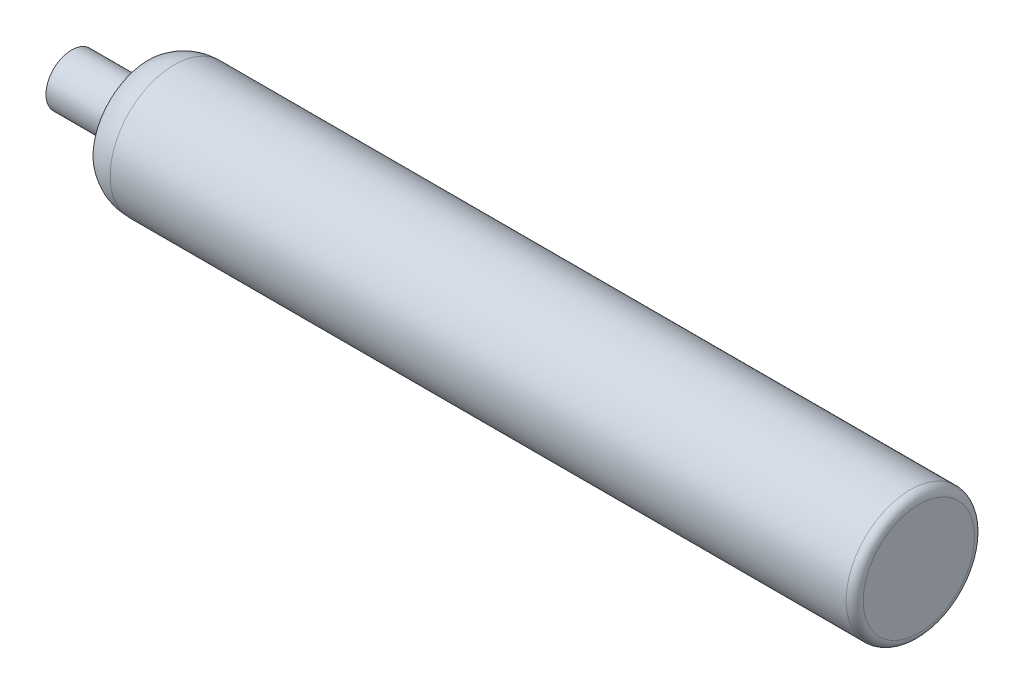
SolidWorks part; units mm, degrees
ref_plane "Front Plane" through (0, 0, 0) normal (0, 0, 1) x (1, 0, 0)
ref_plane "Top Plane" through (0, 0, 0) normal (0, 1, 0) x (1, 0, 0)
ref_plane "Right Plane" through (0, 0, 0) normal (1, 0, 0) x (0, 0, -1)
ref_axis "Axis1" through (0, 0, -88.99) along (0, 0, 1)
ref_axis "Axis2" through (0, -55, 0) along (0, 1, 0)
ref_axis "Axis3" through (-88.99, 0, 0) along (1, 0, 0)
sketch "Sketch1" plane through (0, 0, 0) normal (0, 0, 1) x (1, 0, 0)
  line L0 (0, 0) -> (0, 3)
  line L1 (0, 3) -> (9, 3)
  line L2 (9, 3) -> (9, 7.5)
  line L3 (9, 7.5) -> (99, 7.5)
  line L4 (0, 0) -> (-4.179, 0) construction
  line L5 (0, 0) -> (99, 0)
  line L6 (99, 0) -> (99, 7.5)
  arc A0 (12, 7.5) -> (9, 6.5) centre (12, 2.5) ccw
  arc A1 (99, 6.5) -> (98, 7.5) centre (98, 6.5) ccw
  dimension "D1" = 6
  dimension "D2" = 15
  dimension "D3" = 9
  dimension "D4" = 90
  dimension "D5" = 1
  dimension "D6" = 3
  dimension "D7" = 1
  dimension "D8" = 1
revolve "Revolve1" add sketch "Sketch1" angle 360 about L4 region at (52.1397, 3.6575, 0)
